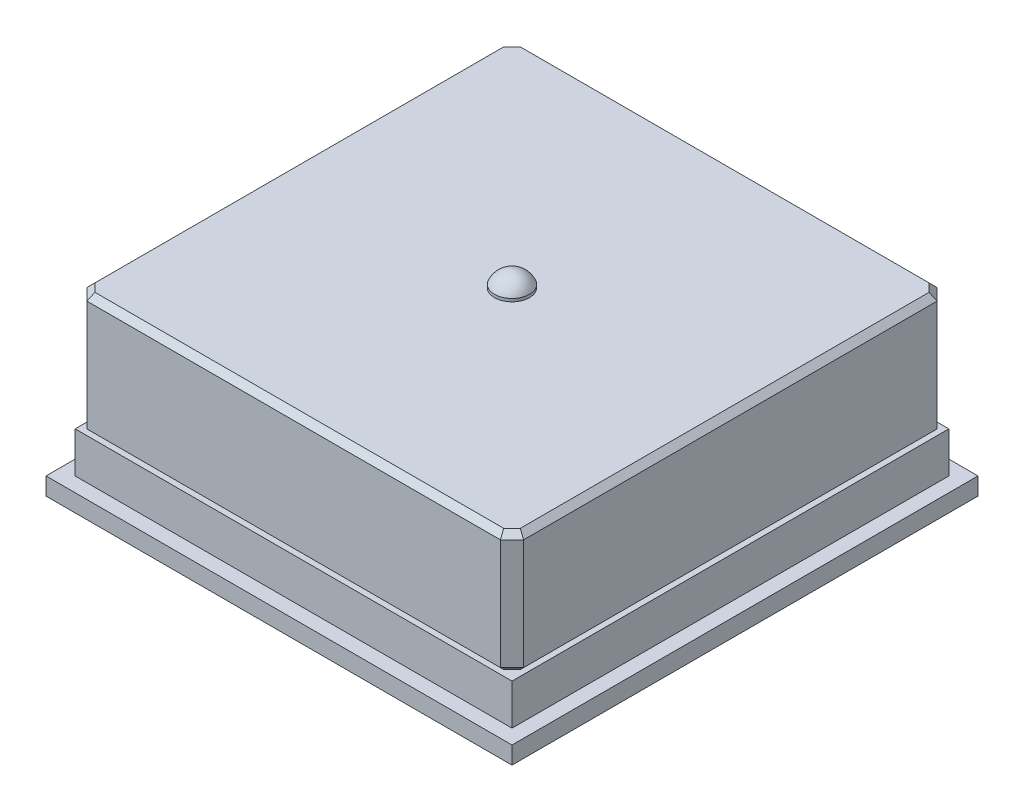
SolidWorks part; units mm, degrees
ref_plane "Front Plane" through (0, 0, 0) normal (0, 0, 1) x (1, 0, 0)
ref_plane "Top Plane" through (0, 0, 0) normal (0, 1, 0) x (1, 0, 0)
ref_plane "Right Plane" through (0, 0, 0) normal (1, 0, 0) x (0, 0, -1)
sketch "Sketch1" plane through (0, 0, 0) normal (0, 1, 0) x (1, 0, 0)
  line L1 (8, -8) -> (-8, -8)
  line L2 (8, -8) -> (8, 8)
  line L3 (8, 8) -> (-8, 8)
  line L4 (-8, -8) -> (-8, 8)
  line L5 (8, -8) -> (-8, 8) construction
  line L6 (8, 8) -> (-8, -8) construction
  point P0 (0, 0)
  dimension "D1" = 16
extrude "Boss-Extrude1" add sketch "Sketch1" along normal blind 0.6
sketch "Sketch2" plane through (0, 0.6, 0) normal (0, 1, 0) x (1, 0, 0)
  line L1 (7.5, -7.5) -> (-7.5, -7.5)
  line L2 (7.5, -7.5) -> (7.5, 7.5)
  line L3 (7.5, 7.5) -> (-7.5, 7.5)
  line L4 (-7.5, -7.5) -> (-7.5, 7.5)
  line L5 (7.5, -7.5) -> (-7.5, 7.5) construction
  line L6 (7.5, 7.5) -> (-7.5, -7.5) construction
  point P0 (0, 0)
  dimension "D1" = 15
extrude "Boss-Extrude2" add sketch "Sketch2" along normal blind 1.4
sketch "Sketch3" plane through (0, 2, 0) normal (0, 1, 0) x (1, 0, 0)
  line L0 (-7.1, 7.5) -> (-7.5, 7.1)
  line L1 (7.5, 7.1) -> (7.1, 7.5)
  line L2 (7.1, -7.5) -> (7.5, -7.1)
  line L3 (-7.5, -7.1) -> (-7.1, -7.5)
  line L4 (-7.5, 7.5) -> (-7.5, -7.5)
  line L5 (-7.5, -7.5) -> (7.5, -7.5)
  line L6 (7.5, -7.5) -> (7.5, 7.5)
  line L7 (7.5, 7.5) -> (-7.5, 7.5)
  line L8 (-7.5, 7.1) -> (-7.5, -7.1)
  line L9 (-7.1, -7.5) -> (7.1, -7.5)
  line L10 (7.5, -7.1) -> (7.5, 7.1)
  line L11 (7.1, 7.5) -> (-7.1, 7.5)
  dimension "D1" = 0
extrude "Boss-Extrude3" add sketch "Sketch3" along normal blind 4.2 separate body
chamfer "Chamfer1" distance 0.2 angle 45 16 edges at (-7.3, 2, 7.3) (0, 2, 7.5) (7.3, 2, 7.3) (7.5, 2, 0) (7.3, 2, -7.3) (0, 2, -7.5) (-7.3, 2, -7.3) (-7.5, 2, 0) (-7.3, 6.2, -7.3) (0, 6.2, -7.5) (7.3, 6.2, -7.3) (7.5, 6.2, 0) (7.3, 6.2, 7.3) (0, 6.2, 7.5) (-7.3, 6.2, 7.3) (-7.5, 6.2, 0)
combine bodies "Combine1" operation type add bodies to combine 103 102
sketch "Sketch4" plane through (0, 6.2, 0) normal (0, 1, 0) x (1, 0, 0)
  circle A0 centre (0, 0) radius 0.6
  dimension "D1" = 1.2
extrude "Boss-Extrude4" add sketch "Sketch4" along normal blind 0.1
dome "Dome1" faces to dome 1 distance 0.4 reverse direction no elliptical dome no face at (0, 6.3, 0.6) parameters "D1"=0.4
sketch "Sketch5" plane through (0, 0, 0) normal (0, -1, 0) x (1, 0, 0)
  line L0 (-8, 8) -> (8, 8) construction
  line L1 (6.9, 7.25) -> (7.7, 7.25)
  line L2 (6.8, 7.15) -> (6.8, 6.35)
  line L3 (6.9, 6.25) -> (7.7, 6.25)
  line L4 (7.8, 7.15) -> (7.8, 6.35)
  line L5 (8, 8) -> (8, -8) construction
  line L6 (6.9, 5.75) -> (7.7, 5.75)
  line L7 (6.8, 5.65) -> (6.8, 4.85)
  line L8 (6.9, 4.75) -> (7.7, 4.75)
  line L9 (7.8, 5.65) -> (7.8, 4.85)
  line L10 (6.9, 4.25) -> (7.7, 4.25)
  line L11 (6.8, 4.15) -> (6.8, 3.35)
  line L12 (6.9, 3.25) -> (7.7, 3.25)
  line L13 (7.8, 4.15) -> (7.8, 3.35)
  line L14 (6.9, 2.75) -> (7.7, 2.75)
  line L15 (6.8, 2.65) -> (6.8, 1.85)
  line L16 (6.9, 1.75) -> (7.7, 1.75)
  line L17 (7.8, 2.65) -> (7.8, 1.85)
  line L18 (6.9, 1.25) -> (7.7, 1.25)
  line L19 (6.8, 1.15) -> (6.8, 0.35)
  line L20 (6.9, 0.25) -> (7.7, 0.25)
  line L21 (7.8, 1.15) -> (7.8, 0.35)
  line L22 (6.9, -0.25) -> (7.7, -0.25)
  line L23 (6.8, -0.35) -> (6.8, -1.15)
  line L24 (6.9, -1.25) -> (7.7, -1.25)
  line L25 (7.8, -0.35) -> (7.8, -1.15)
  line L26 (6.9, -1.75) -> (7.7, -1.75)
  line L27 (6.8, -1.85) -> (6.8, -2.65)
  line L28 (6.9, -2.75) -> (7.7, -2.75)
  line L29 (7.8, -1.85) -> (7.8, -2.65)
  line L30 (6.9, -3.25) -> (7.7, -3.25)
  line L31 (6.8, -3.35) -> (6.8, -4.15)
  line L32 (6.9, -4.25) -> (7.7, -4.25)
  line L33 (7.8, -3.35) -> (7.8, -4.15)
  line L34 (6.9, -4.75) -> (7.7, -4.75)
  line L35 (6.8, -4.85) -> (6.8, -5.65)
  line L36 (6.9, -5.75) -> (7.7, -5.75)
  line L37 (7.8, -4.85) -> (7.8, -5.65)
  line L38 (6.9, -6.25) -> (7.7, -6.25)
  line L39 (6.8, -6.35) -> (6.8, -7.15)
  line L40 (6.9, -7.25) -> (7.7, -7.25)
  line L41 (7.8, -6.35) -> (7.8, -7.15)
  line L42 (8, -8) -> (-8, -8) construction
  line L43 (0, 8) -> (0, -8) construction
  line L44 (-7.8, -6.35) -> (-7.8, -7.15)
  line L45 (-6.9, -7.25) -> (-7.7, -7.25)
  line L46 (-6.8, -6.35) -> (-6.8, -7.15)
  line L47 (-6.9, -6.25) -> (-7.7, -6.25)
  line L48 (-7.8, -4.85) -> (-7.8, -5.65)
  line L49 (-6.9, -5.75) -> (-7.7, -5.75)
  line L50 (-6.8, -4.85) -> (-6.8, -5.65)
  line L51 (-6.9, -4.75) -> (-7.7, -4.75)
  line L52 (-7.8, -3.35) -> (-7.8, -4.15)
  line L53 (-6.9, -4.25) -> (-7.7, -4.25)
  line L54 (-6.8, -3.35) -> (-6.8, -4.15)
  line L55 (-6.9, -3.25) -> (-7.7, -3.25)
  line L56 (-7.8, -1.85) -> (-7.8, -2.65)
  line L57 (-6.9, -2.75) -> (-7.7, -2.75)
  line L58 (-6.8, -1.85) -> (-6.8, -2.65)
  line L59 (-6.9, -1.75) -> (-7.7, -1.75)
  line L60 (-7.8, -0.35) -> (-7.8, -1.15)
  line L61 (-6.9, -1.25) -> (-7.7, -1.25)
  line L62 (-6.8, -0.35) -> (-6.8, -1.15)
  line L63 (-6.9, -0.25) -> (-7.7, -0.25)
  line L64 (-7.8, 1.15) -> (-7.8, 0.35)
  line L65 (-6.9, 0.25) -> (-7.7, 0.25)
  line L66 (-6.8, 1.15) -> (-6.8, 0.35)
  line L67 (-6.9, 1.25) -> (-7.7, 1.25)
  line L68 (-7.8, 2.65) -> (-7.8, 1.85)
  line L69 (-6.9, 1.75) -> (-7.7, 1.75)
  line L70 (-6.8, 2.65) -> (-6.8, 1.85)
  line L71 (-6.9, 2.75) -> (-7.7, 2.75)
  line L72 (-7.8, 4.15) -> (-7.8, 3.35)
  line L73 (-6.9, 3.25) -> (-7.7, 3.25)
  line L74 (-6.8, 4.15) -> (-6.8, 3.35)
  line L75 (-6.9, 4.25) -> (-7.7, 4.25)
  line L76 (-7.8, 5.65) -> (-7.8, 4.85)
  line L77 (-6.9, 4.75) -> (-7.7, 4.75)
  line L78 (-6.8, 5.65) -> (-6.8, 4.85)
  line L79 (-6.9, 5.75) -> (-7.7, 5.75)
  line L80 (-7.8, 7.15) -> (-7.8, 6.35)
  line L81 (-6.9, 6.25) -> (-7.7, 6.25)
  line L82 (-6.8, 7.15) -> (-6.8, 6.35)
  line L83 (-6.9, 7.25) -> (-7.7, 7.25)
  arc A0 (7.7, 6.25) -> (7.8, 6.35) centre (7.7, 6.35) ccw
  arc A1 (6.8, 6.35) -> (6.9, 6.25) centre (6.9, 6.35) ccw
  arc A2 (7.7, 7.25) -> (7.8, 7.15) centre (7.7, 7.15) cw
  arc A3 (6.9, 7.25) -> (6.8, 7.15) centre (6.9, 7.15) ccw
  arc A4 (7.7, 4.75) -> (7.8, 4.85) centre (7.7, 4.85) ccw
  arc A5 (6.8, 4.85) -> (6.9, 4.75) centre (6.9, 4.85) ccw
  arc A6 (7.7, 5.75) -> (7.8, 5.65) centre (7.7, 5.65) cw
  arc A7 (6.9, 5.75) -> (6.8, 5.65) centre (6.9, 5.65) ccw
  arc A8 (7.7, 3.25) -> (7.8, 3.35) centre (7.7, 3.35) ccw
  arc A9 (6.8, 3.35) -> (6.9, 3.25) centre (6.9, 3.35) ccw
  arc A10 (7.7, 4.25) -> (7.8, 4.15) centre (7.7, 4.15) cw
  arc A11 (6.9, 4.25) -> (6.8, 4.15) centre (6.9, 4.15) ccw
  arc A12 (7.7, 1.75) -> (7.8, 1.85) centre (7.7, 1.85) ccw
  arc A13 (6.8, 1.85) -> (6.9, 1.75) centre (6.9, 1.85) ccw
  arc A14 (7.7, 2.75) -> (7.8, 2.65) centre (7.7, 2.65) cw
  arc A15 (6.9, 2.75) -> (6.8, 2.65) centre (6.9, 2.65) ccw
  arc A16 (7.7, 0.25) -> (7.8, 0.35) centre (7.7, 0.35) ccw
  arc A17 (6.8, 0.35) -> (6.9, 0.25) centre (6.9, 0.35) ccw
  arc A18 (7.7, 1.25) -> (7.8, 1.15) centre (7.7, 1.15) cw
  arc A19 (6.9, 1.25) -> (6.8, 1.15) centre (6.9, 1.15) ccw
  arc A20 (7.7, -1.25) -> (7.8, -1.15) centre (7.7, -1.15) ccw
  arc A21 (6.8, -1.15) -> (6.9, -1.25) centre (6.9, -1.15) ccw
  arc A22 (7.7, -0.25) -> (7.8, -0.35) centre (7.7, -0.35) cw
  arc A23 (6.9, -0.25) -> (6.8, -0.35) centre (6.9, -0.35) ccw
  arc A24 (7.7, -2.75) -> (7.8, -2.65) centre (7.7, -2.65) ccw
  arc A25 (6.8, -2.65) -> (6.9, -2.75) centre (6.9, -2.65) ccw
  arc A26 (7.7, -1.75) -> (7.8, -1.85) centre (7.7, -1.85) cw
  arc A27 (6.9, -1.75) -> (6.8, -1.85) centre (6.9, -1.85) ccw
  arc A28 (7.7, -4.25) -> (7.8, -4.15) centre (7.7, -4.15) ccw
  arc A29 (6.8, -4.15) -> (6.9, -4.25) centre (6.9, -4.15) ccw
  arc A30 (7.7, -3.25) -> (7.8, -3.35) centre (7.7, -3.35) cw
  arc A31 (6.9, -3.25) -> (6.8, -3.35) centre (6.9, -3.35) ccw
  arc A32 (7.7, -5.75) -> (7.8, -5.65) centre (7.7, -5.65) ccw
  arc A33 (6.8, -5.65) -> (6.9, -5.75) centre (6.9, -5.65) ccw
  arc A34 (7.7, -4.75) -> (7.8, -4.85) centre (7.7, -4.85) cw
  arc A35 (6.9, -4.75) -> (6.8, -4.85) centre (6.9, -4.85) ccw
  arc A36 (7.7, -7.25) -> (7.8, -7.15) centre (7.7, -7.15) ccw
  arc A37 (6.8, -7.15) -> (6.9, -7.25) centre (6.9, -7.15) ccw
  arc A38 (7.7, -6.25) -> (7.8, -6.35) centre (7.7, -6.35) cw
  arc A39 (6.9, -6.25) -> (6.8, -6.35) centre (6.9, -6.35) ccw
  arc A40 (-6.9, -6.25) -> (-6.8, -6.35) centre (-6.9, -6.35) cw
  arc A41 (-7.7, -6.25) -> (-7.8, -6.35) centre (-7.7, -6.35) ccw
  arc A42 (-6.8, -7.15) -> (-6.9, -7.25) centre (-6.9, -7.15) cw
  arc A43 (-7.7, -7.25) -> (-7.8, -7.15) centre (-7.7, -7.15) cw
  arc A44 (-6.9, -4.75) -> (-6.8, -4.85) centre (-6.9, -4.85) cw
  arc A45 (-7.7, -4.75) -> (-7.8, -4.85) centre (-7.7, -4.85) ccw
  arc A46 (-6.8, -5.65) -> (-6.9, -5.75) centre (-6.9, -5.65) cw
  arc A47 (-7.7, -5.75) -> (-7.8, -5.65) centre (-7.7, -5.65) cw
  arc A48 (-6.9, -3.25) -> (-6.8, -3.35) centre (-6.9, -3.35) cw
  arc A49 (-7.7, -3.25) -> (-7.8, -3.35) centre (-7.7, -3.35) ccw
  arc A50 (-6.8, -4.15) -> (-6.9, -4.25) centre (-6.9, -4.15) cw
  arc A51 (-7.7, -4.25) -> (-7.8, -4.15) centre (-7.7, -4.15) cw
  arc A52 (-6.9, -1.75) -> (-6.8, -1.85) centre (-6.9, -1.85) cw
  arc A53 (-7.7, -1.75) -> (-7.8, -1.85) centre (-7.7, -1.85) ccw
  arc A54 (-6.8, -2.65) -> (-6.9, -2.75) centre (-6.9, -2.65) cw
  arc A55 (-7.7, -2.75) -> (-7.8, -2.65) centre (-7.7, -2.65) cw
  arc A56 (-6.9, -0.25) -> (-6.8, -0.35) centre (-6.9, -0.35) cw
  arc A57 (-7.7, -0.25) -> (-7.8, -0.35) centre (-7.7, -0.35) ccw
  arc A58 (-6.8, -1.15) -> (-6.9, -1.25) centre (-6.9, -1.15) cw
  arc A59 (-7.7, -1.25) -> (-7.8, -1.15) centre (-7.7, -1.15) cw
  arc A60 (-6.9, 1.25) -> (-6.8, 1.15) centre (-6.9, 1.15) cw
  arc A61 (-7.7, 1.25) -> (-7.8, 1.15) centre (-7.7, 1.15) ccw
  arc A62 (-6.8, 0.35) -> (-6.9, 0.25) centre (-6.9, 0.35) cw
  arc A63 (-7.7, 0.25) -> (-7.8, 0.35) centre (-7.7, 0.35) cw
  arc A64 (-6.9, 2.75) -> (-6.8, 2.65) centre (-6.9, 2.65) cw
  arc A65 (-7.7, 2.75) -> (-7.8, 2.65) centre (-7.7, 2.65) ccw
  arc A66 (-6.8, 1.85) -> (-6.9, 1.75) centre (-6.9, 1.85) cw
  arc A67 (-7.7, 1.75) -> (-7.8, 1.85) centre (-7.7, 1.85) cw
  arc A68 (-6.9, 4.25) -> (-6.8, 4.15) centre (-6.9, 4.15) cw
  arc A69 (-7.7, 4.25) -> (-7.8, 4.15) centre (-7.7, 4.15) ccw
  arc A70 (-6.8, 3.35) -> (-6.9, 3.25) centre (-6.9, 3.35) cw
  arc A71 (-7.7, 3.25) -> (-7.8, 3.35) centre (-7.7, 3.35) cw
  arc A72 (-6.9, 5.75) -> (-6.8, 5.65) centre (-6.9, 5.65) cw
  arc A73 (-7.7, 5.75) -> (-7.8, 5.65) centre (-7.7, 5.65) ccw
  arc A74 (-6.8, 4.85) -> (-6.9, 4.75) centre (-6.9, 4.85) cw
  arc A75 (-7.7, 4.75) -> (-7.8, 4.85) centre (-7.7, 4.85) cw
  arc A76 (-6.9, 7.25) -> (-6.8, 7.15) centre (-6.9, 7.15) cw
  arc A77 (-7.7, 7.25) -> (-7.8, 7.15) centre (-7.7, 7.15) ccw
  arc A78 (-6.8, 6.35) -> (-6.9, 6.25) centre (-6.9, 6.35) cw
  arc A79 (-7.7, 6.25) -> (-7.8, 6.35) centre (-7.7, 6.35) cw
  point P10 (7.8, 6.25)
  point P15 (7.8, 7.25)
  dimension "D4" = 0.1
  dimension "D1" = 1
  dimension "D2" = 0.75
  dimension "D3" = 0.2
  dimension "D6" = 0.75
  dimension "D7" = 0.2
  dimension "D5" = 10
split line "Split Line1"
